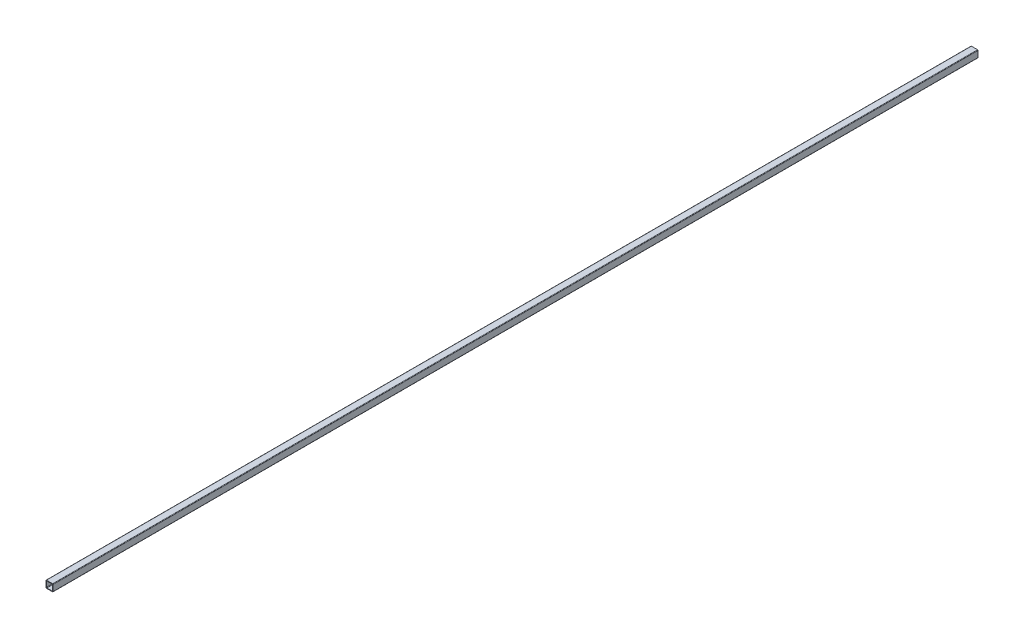
SolidWorks part; units mm, degrees
material "ASTM A500 Grade B"
ref_plane "Front Plane" through (0, 0, 0) normal (0, 0, 1) x (1, 0, 0)
ref_plane "Top Plane" through (0, 0, 0) normal (0, 1, 0) x (1, 0, 0)
ref_plane "Right Plane" through (0, 0, 0) normal (1, 0, 0) x (0, 0, -1)
sketch "Sketch1" plane through (0, 0, 0) normal (0, 0, 1) x (1, 0, 0)
  line L0 (5.3086, -2.7686) -> (32.7914, -2.7686)
  line L1 (2.54, 0) -> (35.56, 0)
  line L2 (0, -2.54) -> (0, -35.56)
  line L3 (2.54, -38.1) -> (35.56, -38.1)
  line L4 (38.1, -2.54) -> (38.1, -35.56)
  line L5 (35.3314, -5.3086) -> (35.3314, -32.7914)
  line L6 (5.3086, -35.3314) -> (32.7914, -35.3314)
  line L7 (2.7686, -5.3086) -> (2.7686, -32.7914)
  line L8 (0, 0) -> (0, -38.1) construction
  line L9 (0, -38.1) -> (38.1, -38.1) construction
  line L10 (38.1, 0) -> (38.1, -38.1) construction
  line L11 (2.7686, -2.7686) -> (2.7686, -35.3314) construction
  line L12 (2.7686, -35.3314) -> (35.3314, -35.3314) construction
  line L13 (35.3314, -2.7686) -> (35.3314, -35.3314) construction
  line L14 (2.7686, -2.7686) -> (35.3314, -2.7686) construction
  line L15 (0, 0) -> (38.1, 0) construction
  arc A0 (0, -35.56) -> (2.54, -38.1) centre (2.54, -35.56) ccw
  arc A1 (38.1, -35.56) -> (35.56, -38.1) centre (35.56, -35.56) cw
  arc A2 (2.7686, -32.7914) -> (5.3086, -35.3314) centre (5.3086, -32.7914) ccw
  arc A3 (32.7914, -35.3314) -> (35.3314, -32.7914) centre (32.7914, -32.7914) ccw
  arc A4 (35.3314, -5.3086) -> (32.7914, -2.7686) centre (32.7914, -5.3086) ccw
  arc A5 (38.1, -2.54) -> (35.56, 0) centre (35.56, -2.54) ccw
  arc A6 (0, -2.54) -> (2.54, 0) centre (2.54, -2.54) cw
  arc A7 (5.3086, -2.7686) -> (2.7686, -5.3086) centre (5.3086, -5.3086) ccw
  point P12 (0, -38.1)
  dimension "D4" = 2.54
  dimension "D3" = 2.7686
extrude "Boss-Extrude1" add sketch "Sketch1" along normal blind 5000
sketch "Sketch2" plane through (0, -38.1, 0) normal (0, -1, 0) x (1, 0, 0)
  line L0 (19.05, 0) -> (19.05, 5000) construction
  line L1 (2.54, 0) -> (35.56, 0) construction
  line L2 (2.54, 5000) -> (35.56, 5000) construction
